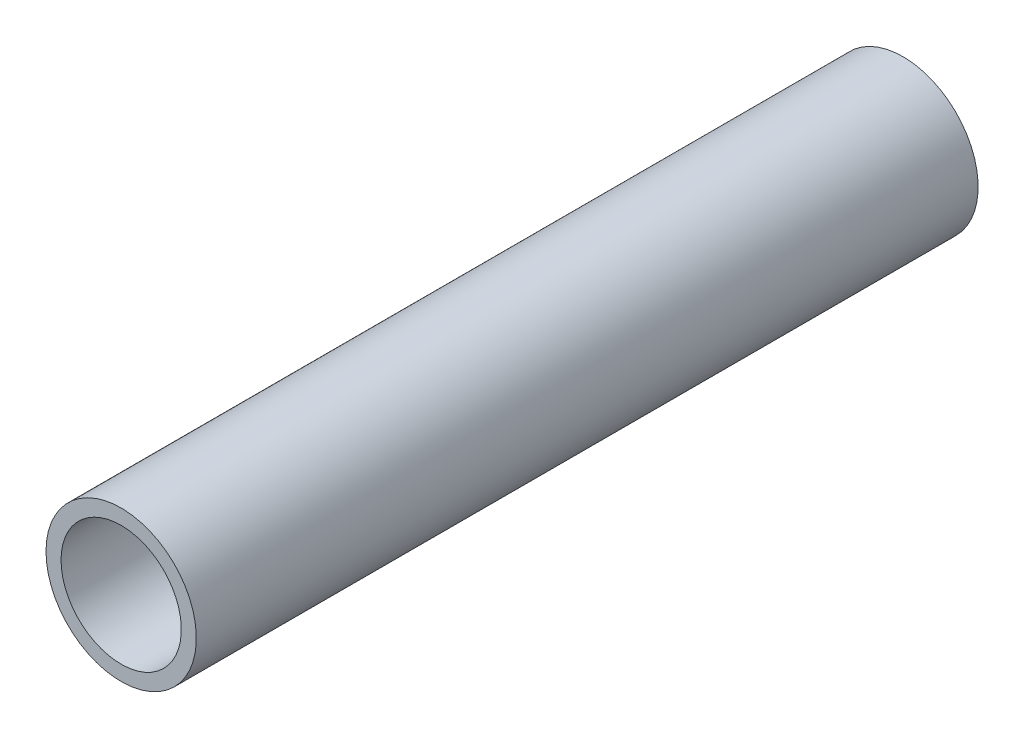
SolidWorks part; units mm, degrees
ref_plane "Front Plane" through (0, 0, 0) normal (0, 0, 1) x (1, 0, 0)
ref_plane "Top Plane" through (0, 0, 0) normal (0, 1, 0) x (1, 0, 0)
ref_plane "Right Plane" through (0, 0, 0) normal (1, 0, 0) x (0, 0, -1)
sketch "Sketch1" plane through (0, 0, 0) normal (0, 0, 1) x (1, 0, 0)
  circle A0 centre (0, 0) radius 1.25
  circle A1 centre (0, 0) radius 1
extrude "Boss-Extrude1" add sketch "Sketch1" along normal blind 13
